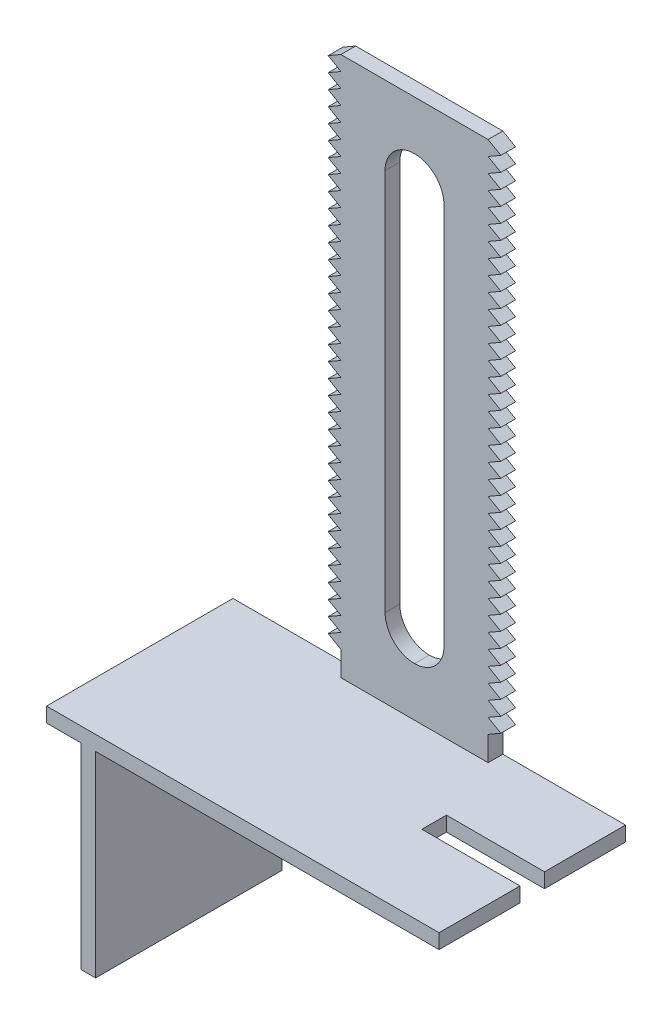
SolidWorks part; units mm, degrees
ref_plane "Front Plane" through (0, 0, 0) normal (0, 0, 1) x (1, 0, 0)
ref_plane "Top Plane" through (0, 0, 0) normal (0, 1, 0) x (1, 0, 0)
ref_plane "Right Plane" through (0, 0, 0) normal (1, 0, 0) x (0, 0, -1)
sketch "Sketch2" plane through (0, 0, 0) normal (0, 1, 0) x (1, 0, 0)
  line L1 (-15, 1.5) -> (15, 1.5)
  line L2 (-15, 1.5) -> (-15, -1.5)
  line L3 (-15, -1.5) -> (15, -1.5)
  line L4 (15, 1.5) -> (15, -1.5)
  line L5 (-15, 1.5) -> (15, -1.5) construction
  line L6 (-15, -1.5) -> (15, 1.5) construction
  point P0 (0, 0)
  dimension "D1" = 30
  dimension "D2" = 3
extrude "Boss-Extrude1" add sketch "Sketch2" along normal blind 110
sketch "Sketch3" plane through (0, 0, 1.5) normal (0, 0, 1) x (1, 0, 0)
  line L0 (15, 110) -> (17.5981, 108.5)
  line L1 (17.5981, 108.5) -> (15, 107)
  line L2 (15, 110) -> (15, 0) construction
  line L3 (15, 107) -> (15, 110)
  line L4 (15, 110) -> (15, 107)
  line L5 (15, 104) -> (15, 107)
  line L6 (17.5981, 105.5) -> (15, 104)
  line L7 (15, 107) -> (17.5981, 105.5)
  line L8 (15, 101) -> (15, 104)
  line L9 (17.5981, 102.5) -> (15, 101)
  line L10 (15, 104) -> (17.5981, 102.5)
  line L11 (15, 98) -> (15, 101)
  line L12 (17.5981, 99.5) -> (15, 98)
  line L13 (15, 101) -> (17.5981, 99.5)
  line L14 (15, 95) -> (15, 98)
  line L15 (17.5981, 96.5) -> (15, 95)
  line L16 (15, 98) -> (17.5981, 96.5)
  line L17 (15, 92) -> (15, 95)
  line L18 (17.5981, 93.5) -> (15, 92)
  line L19 (15, 95) -> (17.5981, 93.5)
  line L20 (15, 89) -> (15, 92)
  line L21 (17.5981, 90.5) -> (15, 89)
  line L22 (15, 92) -> (17.5981, 90.5)
  line L23 (15, 86) -> (15, 89)
  line L24 (17.5981, 87.5) -> (15, 86)
  line L25 (15, 89) -> (17.5981, 87.5)
  line L26 (15, 83) -> (15, 86)
  line L27 (17.5981, 84.5) -> (15, 83)
  line L28 (15, 86) -> (17.5981, 84.5)
  line L29 (15, 80) -> (15, 83)
  line L30 (17.5981, 81.5) -> (15, 80)
  line L31 (15, 83) -> (17.5981, 81.5)
  line L32 (15, 77) -> (15, 80)
  line L33 (17.5981, 78.5) -> (15, 77)
  line L34 (15, 80) -> (17.5981, 78.5)
  line L35 (15, 74) -> (15, 77)
  line L36 (17.5981, 75.5) -> (15, 74)
  line L37 (15, 77) -> (17.5981, 75.5)
  line L38 (15, 71) -> (15, 74)
  line L39 (17.5981, 72.5) -> (15, 71)
  line L40 (15, 74) -> (17.5981, 72.5)
  line L41 (15, 68) -> (15, 71)
  line L42 (17.5981, 69.5) -> (15, 68)
  line L43 (15, 71) -> (17.5981, 69.5)
  line L44 (15, 65) -> (15, 68)
  line L45 (17.5981, 66.5) -> (15, 65)
  line L46 (15, 68) -> (17.5981, 66.5)
  line L47 (15, 62) -> (15, 65)
  line L48 (17.5981, 63.5) -> (15, 62)
  line L49 (15, 65) -> (17.5981, 63.5)
  line L50 (15, 59) -> (15, 62)
  line L51 (17.5981, 60.5) -> (15, 59)
  line L52 (15, 62) -> (17.5981, 60.5)
  line L53 (15, 56) -> (15, 59)
  line L54 (17.5981, 57.5) -> (15, 56)
  line L55 (15, 59) -> (17.5981, 57.5)
  line L56 (15, 53) -> (15, 56)
  line L57 (17.5981, 54.5) -> (15, 53)
  line L58 (15, 56) -> (17.5981, 54.5)
  line L59 (15, 50) -> (15, 53)
  line L60 (17.5981, 51.5) -> (15, 50)
  line L61 (15, 53) -> (17.5981, 51.5)
  line L62 (15, 47) -> (15, 50)
  line L63 (17.5981, 48.5) -> (15, 47)
  line L64 (15, 50) -> (17.5981, 48.5)
  line L65 (15, 44) -> (15, 47)
  line L66 (17.5981, 45.5) -> (15, 44)
  line L67 (15, 47) -> (17.5981, 45.5)
  line L68 (15, 41) -> (15, 44)
  line L69 (17.5981, 42.5) -> (15, 41)
  line L70 (15, 44) -> (17.5981, 42.5)
  line L71 (15, 38) -> (15, 41)
  line L72 (17.5981, 39.5) -> (15, 38)
  line L73 (15, 41) -> (17.5981, 39.5)
  line L74 (15, 35) -> (15, 38)
  line L75 (17.5981, 36.5) -> (15, 35)
  line L76 (15, 38) -> (17.5981, 36.5)
  line L77 (-15, 110) -> (-15, 0) construction
  line L78 (-15, 110) -> (-17.5981, 108.5)
  line L79 (-17.5981, 108.5) -> (-15, 107)
  line L80 (-15, 107) -> (-15, 110)
  line L81 (-17.5981, 105.5) -> (-15, 104)
  line L82 (-15, 107) -> (-17.5981, 105.5)
  line L83 (-15, 104) -> (-15, 107)
  line L84 (-17.5981, 102.5) -> (-15, 101)
  line L85 (-15, 104) -> (-17.5981, 102.5)
  line L86 (-15, 101) -> (-15, 104)
  line L87 (-17.5981, 99.5) -> (-15, 98)
  line L88 (-15, 101) -> (-17.5981, 99.5)
  line L89 (-15, 98) -> (-15, 101)
  line L90 (-17.5981, 96.5) -> (-15, 95)
  line L91 (-15, 98) -> (-17.5981, 96.5)
  line L92 (-15, 95) -> (-15, 98)
  line L93 (-17.5981, 93.5) -> (-15, 92)
  line L94 (-15, 95) -> (-17.5981, 93.5)
  line L95 (-15, 92) -> (-15, 95)
  line L96 (-17.5981, 90.5) -> (-15, 89)
  line L97 (-15, 92) -> (-17.5981, 90.5)
  line L98 (-15, 89) -> (-15, 92)
  line L99 (-17.5981, 87.5) -> (-15, 86)
  line L100 (-15, 89) -> (-17.5981, 87.5)
  line L101 (-15, 86) -> (-15, 89)
  line L102 (-17.5981, 84.5) -> (-15, 83)
  line L103 (-15, 86) -> (-17.5981, 84.5)
  line L104 (-15, 83) -> (-15, 86)
  line L105 (-17.5981, 81.5) -> (-15, 80)
  line L106 (-15, 83) -> (-17.5981, 81.5)
  line L107 (-15, 80) -> (-15, 83)
  line L108 (-17.5981, 78.5) -> (-15, 77)
  line L109 (-15, 80) -> (-17.5981, 78.5)
  line L110 (-15, 77) -> (-15, 80)
  line L111 (-17.5981, 75.5) -> (-15, 74)
  line L112 (-15, 77) -> (-17.5981, 75.5)
  line L113 (-15, 74) -> (-15, 77)
  line L114 (-17.5981, 72.5) -> (-15, 71)
  line L115 (-15, 74) -> (-17.5981, 72.5)
  line L116 (-15, 71) -> (-15, 74)
  line L117 (-17.5981, 69.5) -> (-15, 68)
  line L118 (-15, 71) -> (-17.5981, 69.5)
  line L119 (-15, 68) -> (-15, 71)
  line L120 (-17.5981, 66.5) -> (-15, 65)
  line L121 (-15, 68) -> (-17.5981, 66.5)
  line L122 (-15, 65) -> (-15, 68)
  line L123 (-17.5981, 63.5) -> (-15, 62)
  line L124 (-15, 65) -> (-17.5981, 63.5)
  line L125 (-15, 62) -> (-15, 65)
  line L126 (-17.5981, 60.5) -> (-15, 59)
  line L127 (-15, 62) -> (-17.5981, 60.5)
  line L128 (-15, 59) -> (-15, 62)
  line L129 (-17.5981, 57.5) -> (-15, 56)
  line L130 (-15, 59) -> (-17.5981, 57.5)
  line L131 (-15, 56) -> (-15, 59)
  line L132 (-17.5981, 54.5) -> (-15, 53)
  line L133 (-15, 56) -> (-17.5981, 54.5)
  line L134 (-15, 53) -> (-15, 56)
  line L135 (-17.5981, 51.5) -> (-15, 50)
  line L136 (-15, 53) -> (-17.5981, 51.5)
  line L137 (-15, 50) -> (-15, 53)
  line L138 (-17.5981, 48.5) -> (-15, 47)
  line L139 (-15, 50) -> (-17.5981, 48.5)
  line L140 (-15, 47) -> (-15, 50)
  line L141 (-17.5981, 45.5) -> (-15, 44)
  line L142 (-15, 47) -> (-17.5981, 45.5)
  line L143 (-15, 44) -> (-15, 47)
  line L144 (-17.5981, 42.5) -> (-15, 41)
  line L145 (-15, 44) -> (-17.5981, 42.5)
  line L146 (-15, 41) -> (-15, 44)
  line L147 (-17.5981, 39.5) -> (-15, 38)
  line L148 (-15, 41) -> (-17.5981, 39.5)
  line L149 (-15, 38) -> (-15, 41)
  line L150 (-17.5981, 36.5) -> (-15, 35)
  line L151 (-15, 38) -> (-17.5981, 36.5)
  line L152 (-15, 35) -> (-15, 38)
  line L153 (-17.5981, 33.5) -> (-15, 32)
  line L154 (-15, 35) -> (-17.5981, 33.5)
  line L155 (-15, 32) -> (-15, 35)
  line L156 (17.5981, 33.5) -> (15, 32)
  line L157 (15, 32) -> (15, 35)
  line L158 (15, 35) -> (17.5981, 33.5)
  line L159 (-17.5981, 30.5) -> (-15, 29)
  line L160 (-15, 32) -> (-17.5981, 30.5)
  line L161 (-15, 29) -> (-15, 32)
  line L162 (17.5981, 30.5) -> (15, 29)
  line L163 (15, 29) -> (15, 32)
  line L164 (15, 32) -> (17.5981, 30.5)
  line L165 (-17.5981, 27.5) -> (-15, 26)
  line L166 (-15, 29) -> (-17.5981, 27.5)
  line L167 (-15, 26) -> (-15, 29)
  line L168 (17.5981, 27.5) -> (15, 26)
  line L169 (15, 26) -> (15, 29)
  line L170 (15, 29) -> (17.5981, 27.5)
  line L171 (-17.5981, 24.5) -> (-15, 23)
  line L172 (-15, 26) -> (-17.5981, 24.5)
  line L173 (-15, 23) -> (-15, 26)
  line L174 (17.5981, 24.5) -> (15, 23)
  line L175 (15, 23) -> (15, 26)
  line L176 (15, 26) -> (17.5981, 24.5)
  line L177 (-17.5981, 21.5) -> (-15, 20)
  line L178 (-15, 23) -> (-17.5981, 21.5)
  line L179 (-15, 20) -> (-15, 23)
  line L180 (17.5981, 21.5) -> (15, 20)
  line L181 (15, 20) -> (15, 23)
  line L182 (15, 23) -> (17.5981, 21.5)
  line L183 (-17.5981, 18.5) -> (-15, 17)
  line L184 (-15, 20) -> (-17.5981, 18.5)
  line L185 (-15, 17) -> (-15, 20)
  line L186 (17.5981, 18.5) -> (15, 17)
  line L187 (15, 17) -> (15, 20)
  line L188 (15, 20) -> (17.5981, 18.5)
  line L189 (-17.5981, 15.5) -> (-15, 14)
  line L190 (-15, 17) -> (-17.5981, 15.5)
  line L191 (-15, 14) -> (-15, 17)
  line L192 (17.5981, 15.5) -> (15, 14)
  line L193 (15, 14) -> (15, 17)
  line L194 (15, 17) -> (17.5981, 15.5)
  line L195 (-17.5981, 12.5) -> (-15, 11)
  line L196 (-15, 14) -> (-17.5981, 12.5)
  line L197 (-15, 11) -> (-15, 14)
  line L198 (17.5981, 12.5) -> (15, 11)
  line L199 (15, 11) -> (15, 14)
  line L200 (15, 14) -> (17.5981, 12.5)
  line L201 (-17.5981, 9.5) -> (-15, 8)
  line L202 (-15, 11) -> (-17.5981, 9.5)
  line L203 (-15, 8) -> (-15, 11)
  line L204 (17.5981, 9.5) -> (15, 8)
  line L205 (15, 8) -> (15, 11)
  line L206 (15, 11) -> (17.5981, 9.5)
  line L207 (-17.5981, 6.5) -> (-15, 5)
  line L208 (-15, 8) -> (-17.5981, 6.5)
  line L209 (-15, 5) -> (-15, 8)
  line L210 (17.5981, 6.5) -> (15, 5)
  line L211 (15, 5) -> (15, 8)
  line L212 (15, 8) -> (17.5981, 6.5)
  line M152 (15, 0) -> (15, 110)
  line M154 (-15, 110) -> (-15, 0)
  dimension "D1" = 3
  dimension "D2" = 3
  dimension "D3" = 3
  dimension "D5" = 30
  dimension "D6" = 2.5981
  dimension "D7" = 3
  dimension "D8" = 3
  dimension "D9" = 3
  dimension "D11" = 30
  dimension "D12" = 2.5981
  dimension "D14" = 2.5981
  dimension "D4" = 25
  dimension "D10" = 25
  dimension "D13" = 11
extrude "Boss-Extrude2" add sketch "Sketch3" against normal blind 3 contours L78 L79 M154 | L82 L81 M154 | L85 L84 M154 | L88 L87 M154 | L91 L90 M154 | L94 L93 M154 | L97 L96 M154 | L100 L99 M154 | L103 L102 M154 | L106 L105 M154 | L109 L108 M154 | L1 L0 M152 | L7 L6 M152 | L10 L9 M152 | L13 L12 M152 | L16 L15 M152 | L19 L18 M152 | L22 L21 M152 | L25 L24 M152 | L28 L27 M152 | L31 L30 M152 | L34 L33 M152 | L112 L111 M154 | L115 L114 M154 | L118 L117 M154 | L121 L120 M154 | L124 L123 M154 | L127 L126 M154 | L130 L129 M154 | L133 L132 M154 | L136 L135 M154 | L139 L138 M154 | L142 L141 M154 | L145 L144 M154 | L148 L147 M154 | L151 L150 M154 | L37 L36 M152 | L43 L42 M152 | L46 L45 M152 | L49 L48 M152 | L61 L60 M152 | L64 L63 M152 | L67 L66 M152 | L70 L69 M152 | L73 L72 M152 | L158 L156 M152 | L164 L162 M152 | L154 L153 M154 | L160 L159 M154 | L166 L165 M154 | L172 L171 M154 | L178 L177 M154 | L184 L183 M154 | L170 L168 M152 | L176 L174 M152 | L190 L189 M154 | L182 L180 M152 | L188 L186 M152 | L196 L195 M154 | L194 L192 M152 | L200 L198 M152 | L206 L204 M152 | L212 L210 M152 | L208 L207 M154 | L202 L201 M154 | L40 L39 L38 | L52 L51 L50 | L55 L54 L53 | L58 L57 L56 | L76 L75 L74 region at (15.866, 6.5, 1.5) region at (15.866, 9.5, 1.5) region at (15.866, 12.5, 1.5) region at (15.866, 15.5, 1.5) region at (15.866, 18.5, 1.5) region at (15.866, 21.5, 1.5) region at (15.866, 24.5, 1.5) region at (15.866, 27.5, 1.5) region at (15.866, 30.5, 1.5) region at (15.866, 33.5, 1.5) region at (15.866, 39.5, 1.5) region at (15.866, 42.5, 1.5) region at (15.866, 45.5, 1.5) region at (15.866, 48.5, 1.5) region at (15.866, 51.5, 1.5) region at (15.866, 63.5, 1.5) region at (15.866, 66.5, 1.5) region at (15.866, 69.5, 1.5) region at (15.866, 75.5, 1.5) region at (15.866, 78.5, 1.5) region at (15.866, 81.5, 1.5) region at (15.866, 84.5, 1.5) region at (15.866, 87.5, 1.5) region at (15.866, 90.5, 1.5) region at (15.866, 93.5, 1.5) region at (15.866, 96.5, 1.5) region at (15.866, 99.5, 1.5) region at (15.866, 102.5, 1.5) region at (15.866, 105.5, 1.5) region at (15.866, 108.5, 1.5) region at (-15.866, 108.5, 1.5) region at (-15.866, 6.5, 1.5) region at (-15.866, 9.5, 1.5) region at (-15.866, 12.5, 1.5) region at (-15.866, 15.5, 1.5) region at (-15.866, 18.5, 1.5) region at (-15.866, 21.5, 1.5) region at (-15.866, 24.5, 1.5) region at (-15.866, 27.5, 1.5) region at (-15.866, 30.5, 1.5) region at (-15.866, 33.5, 1.5) region at (-15.866, 36.5, 1.5) region at (-15.866, 39.5, 1.5) region at (-15.866, 42.5, 1.5) region at (-15.866, 45.5, 1.5) region at (-15.866, 48.5, 1.5) region at (-15.866, 51.5, 1.5) region at (-15.866, 54.5, 1.5) region at (-15.866, 57.5, 1.5) region at (-15.866, 60.5, 1.5) region at (-15.866, 63.5, 1.5) region at (-15.866, 66.5, 1.5) region at (-15.866, 69.5, 1.5) region at (-15.866, 72.5, 1.5) region at (-15.866, 75.5, 1.5) region at (-15.866, 78.5, 1.5) region at (-15.866, 81.5, 1.5) region at (-15.866, 84.5, 1.5) region at (-15.866, 87.5, 1.5) region at (-15.866, 90.5, 1.5)
sketch "Sketch4" plane through (0, 0, 1.5) normal (0, 0, 1) x (1, 0, 0)
  line L0 (-9, 0) -> (-9, -3)
  line L1 (-15, 0) -> (15, 0)
  line L2 (-15, 0) -> (-15, -6)
  line L3 (-15, -6) -> (15, -6)
  line L4 (15, 0) -> (15, -6)
  line L5 (-15, 0) -> (-12, 0)
  line L6 (-15, 0) -> (-15, -3)
  line L7 (-15, -3) -> (-12, -3)
  line L8 (-12, 0) -> (-12, -3)
  line L9 (-12, -3) -> (-9, -3)
  line L10 (-6, 0) -> (-6, -3)
  line L11 (-9, -3) -> (-6, -3)
  line L12 (-3, 0) -> (-3, -3)
  line L13 (-6, -3) -> (-3, -3)
  line L14 (0, 0) -> (0, -3)
  line L15 (-3, -3) -> (0, -3)
  line L16 (3, 0) -> (3, -3)
  line L17 (0, -3) -> (3, -3)
  line L18 (6, 0) -> (6, -3)
  line L19 (3, -3) -> (6, -3)
  line L20 (9, 0) -> (9, -3)
  line L21 (6, -3) -> (9, -3)
  line L22 (12, 0) -> (12, -3)
  line L23 (9, -3) -> (12, -3)
  line L24 (15, 0) -> (15, -3)
  line L25 (12, -3) -> (15, -3)
  dimension "D1" = 6
  dimension "D2" = 30
  dimension "D3" = 3
  dimension "D4" = 3
  dimension "D6" = 6
  dimension "D7" = 3
  dimension "D5" = 10
extrude "Boss-Extrude3" add sketch "Sketch4" against normal blind 3 contours L25 L23 L21 L19 L17 L15 L13 L11 L9 L7 L2 L3 L4 | L8 L1 L2 L7 | L0 L11 L10 L1 | L12 L15 L14 L1 | L14 L17 L16 L1 | L18 L21 L20 L1 | L22 L25 L4 L1 region at (-7.5, -1.5, 1.5) region at (0, -4.5, 1.5) region at (-13.5, -1.5, 1.5) region at (-1.5, -1.5, 1.5) region at (1.5, -1.5, 1.5) region at (7.5, -1.5, 1.5) region at (13.5, -1.5, 1.5)
sketch "Sketch5" plane through (0, 0, -1.5) normal (0, 0, -1) x (-1, 0, 0)
  line L0 (-15, 5) -> (-15, -6) construction
  line L1 (-6, 100) -> (6, 100)
  line L2 (-6, 100) -> (-6, 10)
  line L3 (-6, 10) -> (6, 10)
  line L4 (6, 100) -> (6, 10)
  line L5 (15, -6) -> (-15, -6) construction
  dimension "D1" = 12
  dimension "D2" = 90
  dimension "D3" = 9
  dimension "D4" = 16
extrude "Cut-Extrude1" cut sketch "Sketch5" against normal blind 3
fillet "Fillet1" radius 6 4 edges at (-6, 10, 0) (6, 10, 0) (6, 100, 0) (-6, 100, 0)
sketch "Sketch7" plane through (0, 0, 1.5) normal (0, 0, 1) x (1, 0, 0)
  line L0 (-15, 5) -> (-15, -6) construction
  line L1 (-15, 0) -> (15, 0)
  line L2 (-15, 0) -> (-15, -3)
  line L3 (-15, -3) -> (15, -3)
  line L4 (15, 0) -> (15, -3)
  line L5 (15, 5) -> (15, -6) construction
  line L6 (-15, -6) -> (15, -6) construction
  line L8 (-15, 0) -> (-12, 0)
  line L9 (-15, 0) -> (-15, -3)
  line L10 (-15, -3) -> (-12, -3)
  line L11 (-12, 0) -> (-12, -3)
  line L12 (-12, -3) -> (-9, -3)
  line L13 (-12, -3) -> (-12, 0)
  line L14 (-12, 0) -> (-9, 0)
  line L15 (-9, -3) -> (-9, 0)
  line L16 (-9, 0) -> (-6, 0)
  line L17 (-9, 0) -> (-9, -3)
  line L18 (-9, -3) -> (-6, -3)
  line L19 (-6, 0) -> (-6, -3)
  line L20 (-6, -3) -> (-3, -3)
  line L21 (-6, -3) -> (-6, 0)
  line L22 (-6, 0) -> (-3, 0)
  line L23 (-3, -3) -> (-3, 0)
  line L24 (-3, 0) -> (3, 0)
  line L25 (-3, 0) -> (-3, -3)
  line L26 (-3, -3) -> (3, -3)
  line L27 (3, 0) -> (3, -3)
  line L28 (3, -3) -> (6, -3)
  line L29 (3, -3) -> (3, 0)
  line L30 (3, 0) -> (6, 0)
  line L31 (6, -3) -> (6, 0)
  line L32 (6, 0) -> (9, 0)
  line L33 (6, 0) -> (6, -3)
  line L34 (6, -3) -> (9, -3)
  line L35 (9, 0) -> (9, -3)
  line L36 (9, -3) -> (12, -3)
  line L37 (9, -3) -> (9, 0)
  line L38 (9, 0) -> (12, 0)
  line L39 (12, -3) -> (12, 0)
  line L40 (12, 0) -> (15, 0)
  line L41 (12, 0) -> (12, -3)
  line L42 (12, -3) -> (15, -3)
  line L43 (15, 0) -> (15, -3)
  dimension "D1" = 3
  dimension "D2" = 3
extrude "Boss-Extrude8" add sketch "Sketch7" along normal blind 10 contours L11 L1 L2 L3 | L19 L1 L15 L3 | L27 L1 L23 L3 | L35 L1 L31 L3 | L39 L3 L4 L1 region at (-13.5, -1.5, 1.5) region at (-7.5, -1.5, 1.5) region at (0, -1.5, 1.5) region at (7.5, -1.5, 1.5) region at (13.5, -1.5, 1.5)
sketch "Sketch8" plane through (-9, 0, 0) normal (-1, 0, 0) x (0, 0, 1)
  line L1 (-1.5, 0) -> (11.5, 0)
  line L2 (-1.5, 0) -> (-1.5, -3)
  line L3 (-1.5, -3) -> (11.5, -3)
  line L4 (11.5, 0) -> (11.5, -3)
extrude "Boss-Extrude9" add sketch "Sketch8" along normal blind 3
sketch "Sketch9" plane through (-3, 0, 0) normal (-1, 0, 0) x (0, 0, 1)
  line L1 (-1.5, 0) -> (11.5, 0)
  line L2 (-1.5, 0) -> (-1.5, -3)
  line L3 (-1.5, -3) -> (11.5, -3)
  line L4 (11.5, 0) -> (11.5, -3)
extrude "Boss-Extrude10" add sketch "Sketch9" along normal blind 3
sketch "Sketch10" plane through (6, 0, 0) normal (-1, 0, 0) x (0, 0, 1)
  line L1 (-1.5, 0) -> (11.5, 0)
  line L2 (-1.5, 0) -> (-1.5, -3)
  line L3 (-1.5, -3) -> (11.5, -3)
  line L4 (11.5, 0) -> (11.5, -3)
extrude "Boss-Extrude11" add sketch "Sketch10" along normal blind 3
sketch "Sketch11" plane through (12, 0, 0) normal (-1, 0, 0) x (0, 0, 1)
  line L1 (-1.5, 0) -> (11.5, 0)
  line L2 (-1.5, 0) -> (-1.5, -3)
  line L3 (-1.5, -3) -> (11.5, -3)
  line L4 (11.5, 0) -> (11.5, -3)
extrude "Boss-Extrude12" add sketch "Sketch11" along normal blind 3
sketch "Sketch12" plane through (-15, 0, 0) normal (-1, 0, 0) x (0, 0, 1)
  line L0 (-1.5, 5) -> (-1.5, -6) construction
  line L1 (11.5, 0) -> (-1.5, 0)
  line L2 (11.5, 0) -> (11.5, -3)
  line L3 (11.5, -3) -> (-1.5, -3)
  line L4 (-1.5, 0) -> (-1.5, -3)
  dimension "D1" = 3
extrude "Boss-Extrude13" add sketch "Sketch12" along normal blind 25
sketch "Sketch13" plane through (15, 0, 0) normal (1, 0, 0) x (0, 0, -1)
  line L0 (1.5, 5) -> (1.5, -6) construction
  line L1 (-11.5, 0) -> (1.5, 0)
  line L2 (-11.5, 0) -> (-11.5, -3)
  line L3 (-11.5, -3) -> (1.5, -3)
  line L4 (1.5, 0) -> (1.5, -3)
  dimension "D1" = 3
extrude "Boss-Extrude14" add sketch "Sketch13" along normal blind 25
sketch "Sketch14" plane through (0, 0, 11.5) normal (0, 0, 1) x (1, 0, 0)
  line L1 (-40, 0) -> (40, 0)
  line L2 (-40, 0) -> (-40, -3)
  line L3 (-40, -3) -> (40, -3)
  line L4 (40, 0) -> (40, -3)
extrude "Boss-Extrude15" add sketch "Sketch14" along normal blind 25
sketch "Sketch15" plane through (0, -3, 0) normal (0, -1, 0) x (1, 0, 0)
  line L0 (-40, 36.5) -> (40, 36.5) construction
  line L1 (-33, 36.5) -> (-30, 36.5)
  line L2 (-33, 36.5) -> (-33, -1.5)
  line L3 (-33, -1.5) -> (-30, -1.5)
  line L4 (-30, 36.5) -> (-30, -1.5)
  line L5 (-40, -1.5) -> (-15, -1.5) construction
  line L6 (-15, -1.5) -> (-15, 1.5) construction
  dimension "D1" = 3
  dimension "D2" = 15
extrude "Boss-Extrude16" add sketch "Sketch15" along normal blind 40
sketch "Sketch16" plane through (0, -3, 0) normal (0, -1, 0) x (1, 0, 0)
  line L0 (40, 36.5) -> (40, -1.5) construction
  line L1 (40, 20) -> (20, 20)
  line L2 (40, 20) -> (40, 15)
  line L3 (40, 15) -> (20, 15)
  line L4 (20, 20) -> (20, 15)
  line L7 (40, -1.5) -> (15, -1.5) construction
  dimension "D1" = 5
  dimension "D2" = 20
  dimension "D3" = 16.5
extrude "Cut-Extrude2" cut sketch "Sketch16" against normal blind 3
